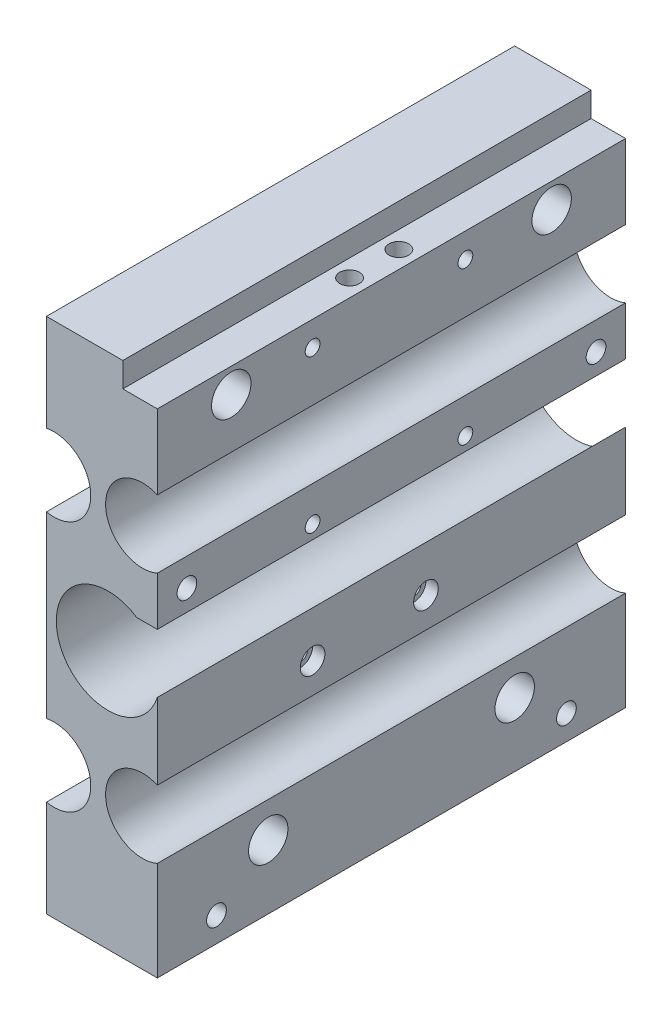
SolidWorks part; units mm, degrees
material "ABS"
ref_plane "Front Plane" through (0, 0, 0) normal (0, 0, 1) x (1, 0, 0)
ref_plane "Top Plane" through (0, 0, 0) normal (0, 1, 0) x (1, 0, 0)
ref_plane "Right Plane" through (0, 0, 0) normal (1, 0, 0) x (0, 0, -1)
sketch "Sketch1" plane through (0, 0, 0) normal (0, 0, 1) x (1, 0, 0)
  line L0 (0, 0) -> (8, 0)
  line L1 (8, 0) -> (8, -5)
  line L2 (8, -5) -> (15, -5)
  line L3 (15, -5) -> (15, -9.75)
  line L5 (15, -43.75) -> (7, -43.75)
  line L6 (7, -43.75) -> (7, -53.25)
  line L7 (7, -53.25) -> (15, -53.25)
  line L8 (15, -53.25) -> (15, -60.75)
  line L9 (15, -60.75) -> (15, -105)
  line L10 (15, -105) -> (0, -105)
  line L11 (0, -105) -> (0, 0)
  line L19 (15, -24.75) -> (15, -43.75)
  line L20 (15, -9.75) -> (15, -24.75)
  dimension "D2" = 15
  dimension "D8" = 15
  dimension "D3" = 105
  dimension "D4" = 9.75
  dimension "D5" = 19
  dimension "D6" = 7.5
  dimension "D7" = 5
  dimension "D9" = 8
  dimension "D10" = 8
  dimension "D11" = 9.5
extrude "Boss-Extrude1" add sketch "Sketch1" along normal blind 95
ref_plane "Plane3" through (0, 0, 47.5) normal (0, 0, 1) x (1, 0, 0)
ref_plane "Plan1" through (0, -52.5, 0) normal (0, 1, 0) x (1, 0, 0)
ref_plane "Plane4" through (0, -50, 0) normal (0, 1, 0) x (1, 0, 0)
sketch "Sketch17" plane through (0, 0, 0) normal (-1, 0, 0) x (0, 0, 1)
  line L1 (0, 0) -> (95, 0)
  line L2 (0, 0) -> (0, -105)
  line L3 (0, -105) -> (95, -105)
  line L4 (95, 0) -> (95, -105)
extrude "Boss-Extrude3" add sketch "Sketch17" along normal blind 7.5
sketch "Sketch18" plane through (0, 0, 95) normal (0, 0, 1) x (1, 0, 0)
  line L0 (4.4, -52.5) -> (-4.4, -52.5) construction
  line L3 (15, -43.75) -> (15, -5) construction
  circle A0 centre (-6, -27) radius 7.5
  circle A1 centre (-6, -78) radius 7.5
  dimension "D1" = 15
  dimension "D2" = 51
  dimension "D3" = 25.5
  dimension "D4" = 21
extrude "Cut-Extrude3" cut sketch "Sketch18" against normal through all
sketch "Esquisse1" plane through (15, 0, 0) normal (1, 0, 0) x (0, 0, -1)
  line L1 (-95, -105) -> (0, -105) construction
  line L2 (-95, -105) -> (-95, -53.25) construction
  line L4 (-47.5, 12.375) -> (-47.5, -12.375) construction
  circle A0 centre (-83, -100) radius 2
  circle A2 centre (-12, -100) radius 2
  dimension "D1" = 4
  dimension "D2" = 5
  dimension "D3" = 12
extrude "Enlèv. mat.-Extru.1" cut sketch "Esquisse1" against normal through all
sketch "Esquisse3" plane through (15, 0, 0) normal (1, 0, 0) x (0, 0, -1)
  line L0 (0, -43.75) -> (0, -5) construction
  line L1 (-95, -43.75) -> (-95, -5) construction
  line L2 (-95, 0) -> (0, 0) construction
  circle A0 centre (-6, -39.5) radius 2
  circle A1 centre (-89, -39.5) radius 2
  dimension "D1" = 6
  dimension "D2" = 6
  dimension "D3" = 4
  dimension "D4" = 39.5
extrude "Enlèv. mat.-Extru.3" cut sketch "Esquisse3" against normal through all
sketch "Esquisse4" plane through (0, 0, 0) normal (0, 0, -1) x (-1, 0, 0)
  line L0 (8.525, -52.5) -> (-8.525, -52.5) construction
  circle A0 centre (-12, -78) radius 7.5
  arc A1 (7.5, -70.6515) -> (7.5, -85.3485) centre (6, -78) ccw construction
  circle A2 centre (-12, -27) radius 7.5
  circle A4 centre (-5, -52.5) radius 10.5
  dimension "D1" = 18
  dimension "D2" = 25.5
  dimension "D3" = 25.5
  dimension "D4" = 7
  dimension "D5" = 25.5
  dimension "D6" = 21
extrude "Enlèv. mat.-Extru.4" cut sketch "Esquisse4" against normal through all
sketch "Esquisse5" plane through (-7.5, 0, 0) normal (1, 0, 0) x (0, 0, -1)
  line L0 (0, -20.1261) -> (0, -5) construction
  line L1 (-95, 0) -> (0, 0) construction
  line L2 (-47.5, 12.375) -> (-47.5, -12.375) construction
  circle A0 centre (-15, -10) radius 4
  circle A1 centre (-80, -10) radius 4
  circle A4 centre (-22.5, -92) radius 4
  circle A5 centre (-72.5, -92) radius 4
  circle A6 centre (-80, -45) radius 4 [skipped]
  circle A7 centre (-15, -45) radius 4 [skipped]
  dimension "D1" = 8
  dimension "D4" = 7.5
  dimension "D5" = 15
  dimension "D6" = 10
  dimension "D8" = 65
  dimension "D9" = 82
  dimension "D2" = 2
  dimension "D3" = 2
extrude "Enlèv. mat.-Extru.15CNC" cut sketch "Esquisse5" along normal through all
sketch "Esquisse6" plane through (15, 0, 0) normal (1, 0, 0) x (0, 0, -1)
  line L3 (-47.5, 12.375) -> (-47.5, -12.375) construction
  line L5 (8.525, -52.5) -> (-8.525, -52.5) construction
  circle A0 centre (-32.5, -10) radius 1.5
  circle A1 centre (-63.5, -10) radius 1.5
  circle A2 centre (-63.5, -41) radius 1.5
  circle A3 centre (-32.5, -41) radius 1.5
  circle A4 centre (-40.5, -65) radius 1.5
  circle A5 centre (-63.5, -65) radius 1.5
  dimension "D1" = 42.5
  dimension "D2" = 15
  dimension "D3" = 2
  dimension "D5" = 3
  dimension "D6" = 31
  dimension "D7" = 31
  dimension "D8" = 8
  dimension "D9" = 55
  dimension "D11" = 23
  dimension "D4" = 2
  dimension "D10" = 2
extrude "Enlèv. mat.-Extru.19" cut sketch "Esquisse6" against normal through all
sketch "Esquisse8" plane through (0, -5, 0) normal (0, 1, 0) x (1, 0, 0)
  line L0 (-12.375, -47.5) -> (12.375, -47.5) construction
  line L2 (8, -95) -> (8, 0) construction
  circle A0 centre (11.5, -42.5) radius 2
  circle A1 centre (11.5, -52.5) radius 2
  circle A2 centre (11.5, -42.5) radius 3
  circle A3 centre (11.5, -52.5) radius 3
  dimension "D1" = 5
  dimension "D2" = 10
  dimension "D3" = 3.5
  dimension "D4" = 4
  dimension "D5" = 6
extrude "Enlèv. mat.-Extru.20" cut sketch "Esquisse8" against normal blind 15 contours A0 | A1
extrude "Enlèv. mat.-Extru.21" cut sketch "Esquisse8<3>" against normal blind 10 from offset 10 contours A2 A0 | A3 A1 region at (8.5849, -5, 42.5) region at (8.5849, -5, 52.5) offset against normal yes
sketch "Esquisse8<3>" plane through (0, -5, 0) normal (0, 1, 0) x (1, 0, 0) same geometry as "Esquisse8"
sketch "Esquisse9" plane through (15, 0, 0) normal (1, 0, 0) x (0, 0, -1)
  circle A0 centre (-40.5, -65) radius 2.5
  circle A1 centre (-63.5, -65) radius 2.5
  dimension "D1" = 5
extrude "Enlèv. mat.-Extru.22" cut sketch "Esquisse9" against normal blind 2.5
